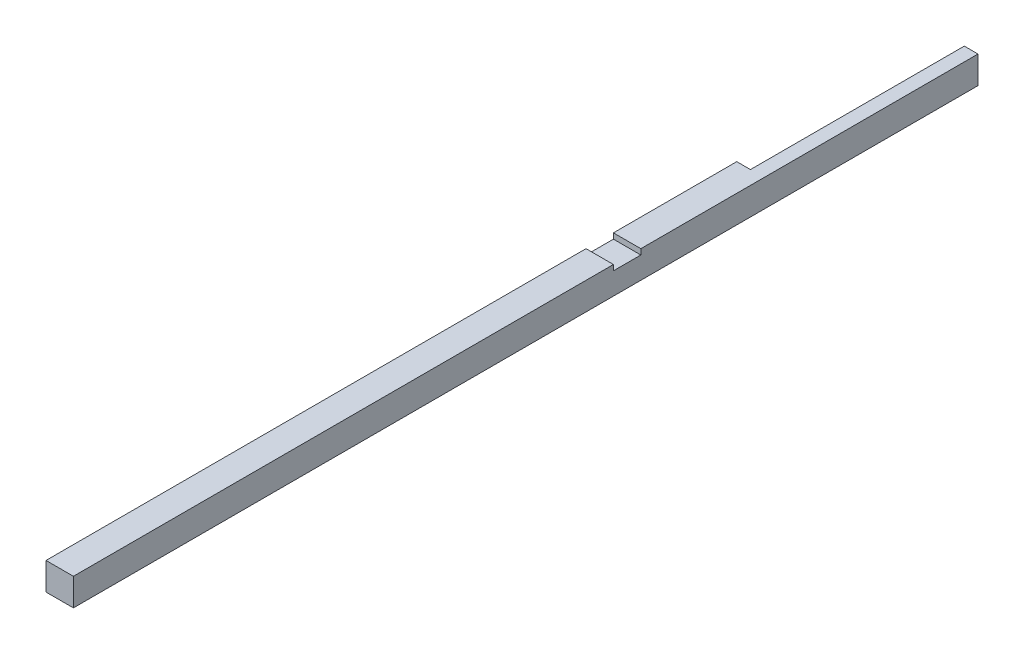
SolidWorks part; units mm, degrees
ref_plane "Plan de face" through (0, 0, 0) normal (0, 0, 1) x (1, 0, 0)
ref_plane "Plan de dessus" through (0, 0, 0) normal (0, 1, 0) x (1, 0, 0)
ref_plane "Plan de droite" through (0, 0, 0) normal (1, 0, 0) x (0, 0, -1)
sketch "Esquisse1" plane through (0, 0, 0) normal (0, 0, 1) x (1, 0, 0)
  line L0 (-5, 5) -> (5, -5) construction
  line L1 (-5, 5) -> (5, 5)
  line L2 (-5, 5) -> (-5, -5)
  line L3 (-5, -5) -> (5, -5)
  line L4 (5, 5) -> (5, -5)
  dimension "D1" = 10
extrude "Boss.-Extru.1" add sketch "Esquisse1" along normal offset from surface (337 mm away) 2 offset beyond the face yes
sketch "Esquisse2" plane through (0, 0, 0) normal (0, 1, 0) x (1, 0, 0)
  line L0 (-5, -85.0125) -> (0, -85.0125)
  line L1 (0, -85.0125) -> (0, -7)
  line L2 (0, -7) -> (5, -7)
  line L3 (5, -7) -> (5, 0)
  line L4 (5, 0) -> (-5, 0)
  line L5 (-5, 0) -> (-5, -85.0125)
  line L6 (5, -337) -> (5, 0) construction
  line L7 (-5, -337) -> (-5, 0) construction
  line L8 (-14, -82.0125) -> (0, -82.0125) construction
  dimension "D1" = 3
  dimension "D2" = 7
extrude "Enlèv. mat.-Extru.1" cut sketch "Esquisse2" against normal through all and the other way through all
sketch "Esquisse4" plane through (5, 0, 0) normal (1, 0, 0) x (0, 0, -1)
  line L0 (-140, 239) -> (-140, 3) construction
  line L1 (-140, 5) -> (-130, 5)
  line L2 (-140, 5) -> (-140, 3)
  line L3 (-140, 3) -> (-130, 3)
  line L4 (-130, 5) -> (-130, 3)
  line L5 (-130, 239) -> (-130, 3) construction
  line L6 (-337, 5) -> (-7, 5) construction
  dimension "D1" = 2
extrude "Enlèv. mat.-Extru.3" cut sketch "Esquisse4" against normal through all
sketch "Esquisse5" plane through (5, 0, 0) normal (1, 0, 0) x (0, 0, -1)
  line L0 (-337, -5) -> (-7, -5) construction
  line L1 (-130, -5) -> (-140, -5)
  line L2 (-130, -5) -> (-130, -3)
  line L3 (-130, -3) -> (-140, -3)
  line L4 (-140, -5) -> (-140, -3)
  line L7 (-140, 3) -> (-140, 239) construction
  line L8 (-130, 3) -> (-130, 239) construction
  dimension "D1" = 2
extrude "Enlèv. mat.-Extru.4" [suppressed] cut sketch "Esquisse5" against normal through all
